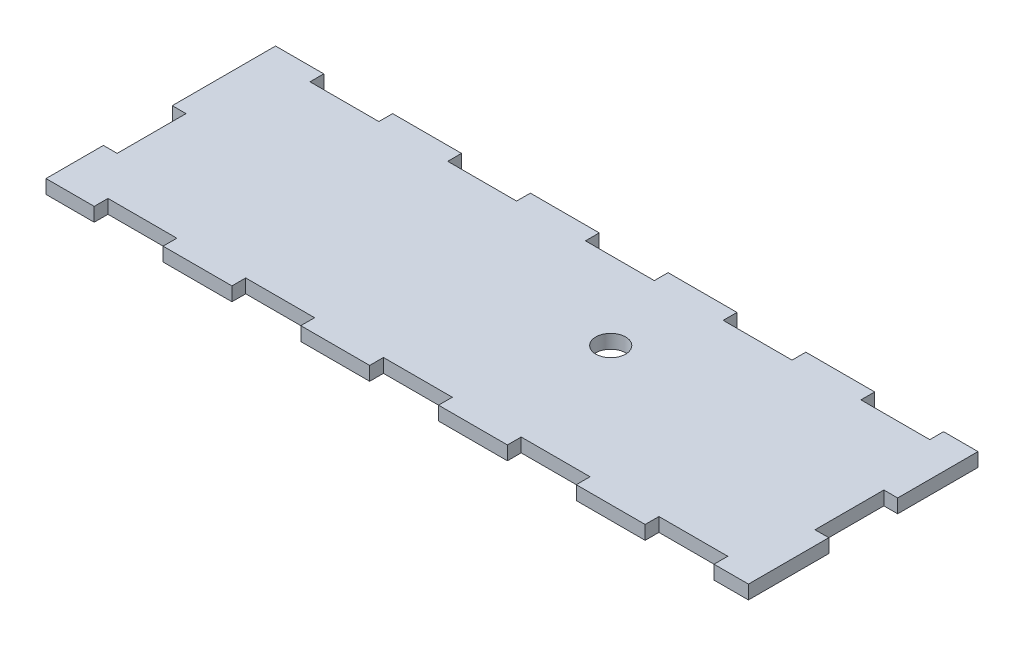
SolidWorks part; units mm, degrees
ref_plane "Alzado" through (0, 0, 0) normal (0, 0, 1) x (1, 0, 0)
ref_plane "Planta" through (0, 0, 0) normal (0, 1, 0) x (1, 0, 0)
ref_plane "Vista lateral" through (0, 0, 0) normal (1, 0, 0) x (0, 0, -1)
sketch "Croquis1" plane through (0, 0, 0) normal (0, 1, 0) x (1, 0, 0)
  line L0 (0, 0) -> (10.5, 0)
  line L1 (0, 40) -> (0, 50)
  line L2 (3, 50) -> (10.5, 50)
  line L3 (153, 50) -> (153, 32.5)
  line L4 (0, 0) -> (0, 12.5)
  line L6 (3, 20) -> (3, 27.5)
  line L7 (3, 27.5) -> (0, 27.5)
  line L8 (3, 20) -> (3, 12.5)
  line L9 (3, 12.5) -> (0, 12.5)
  line L11 (3, 50) -> (10.5, 50)
  line L12 (93, 50) -> (93, 30) construction
  line L13 (0, 27.5) -> (0, 40)
  line L14 (70.5, 50) -> (67.6088, 50)
  line L15 (85.5, 47) -> (70.5, 47)
  line L16 (70.5, 47) -> (70.5, 50)
  line L17 (70.5, 50) -> (55.5, 50)
  line L18 (55.5, 50) -> (55.5, 47)
  line L19 (55.5, 47) -> (40.5, 47)
  line L20 (40.5, 47) -> (40.5, 50)
  line L21 (40.5, 50) -> (25.5, 50)
  line L22 (25.5, 50) -> (25.5, 47)
  line L23 (25.5, 47) -> (10.5, 47)
  line L24 (10.5, 47) -> (10.5, 50)
  line L25 (145.5, 47) -> (145.5, 50)
  line L26 (130.5, 47) -> (145.5, 47)
  line L27 (130.5, 50) -> (130.5, 47)
  line L28 (115.5, 47) -> (115.5, 50)
  line L29 (100.5, 47) -> (115.5, 47)
  line L30 (100.5, 50) -> (100.5, 47)
  line L31 (85.5, 47) -> (85.5, 50)
  line L32 (0, 50) -> (3, 50)
  line L33 (150, 25) -> (150, 32.5)
  line L34 (150, 32.5) -> (153, 32.5)
  line L35 (150, 25) -> (150, 17.5)
  line L36 (150, 17.5) -> (153, 17.5)
  line L37 (25.5, 0) -> (40.5, 0)
  line L38 (85.5, 3) -> (85.5, 0)
  line L39 (100.5, 0) -> (100.5, 3)
  line L40 (100.5, 3) -> (115.5, 3)
  line L41 (115.5, 3) -> (115.5, 0)
  line L42 (130.5, 0) -> (130.5, 3)
  line L43 (130.5, 3) -> (145.5, 3)
  line L44 (145.5, 3) -> (145.5, 0)
  line L45 (10.5, 3) -> (10.5, 0)
  line L46 (25.5, 3) -> (10.5, 3)
  line L47 (25.5, 0) -> (25.5, 3)
  line L48 (40.5, 3) -> (40.5, 0)
  line L49 (55.5, 3) -> (40.5, 3)
  line L50 (55.5, 0) -> (55.5, 3)
  line L51 (70.5, 3) -> (70.5, 0)
  line L52 (85.5, 3) -> (70.5, 3)
  line L53 (55.5, 0) -> (70.5, 0)
  line L54 (85.5, 0) -> (100.5, 0)
  line L55 (115.5, 0) -> (130.5, 0)
  line L56 (145.5, 0) -> (153, 0)
  line L57 (153, 17.5) -> (153, 0)
  line L58 (145.5, 50) -> (153, 50)
  line L59 (115.5, 50) -> (130.5, 50)
  line L60 (85.5, 50) -> (100.5, 50)
  line L61 (85.5, 50) -> (93, 50)
  line L62 (55.5, 50) -> (70.5, 50)
  line L63 (55.5, 50) -> (70.5, 50)
  line L64 (25.5, 50) -> (40.5, 50)
  line L65 (25.5, 50) -> (40.5, 50)
  circle A0 centre (93, 30) radius 3.25
  dimension "D9" = 6.5
  dimension "D1" = 153
  dimension "D3" = 40
  dimension "D5" = 7.5
  dimension "D6" = 7.5
  dimension "D7" = 90
  dimension "D8" = 20
  dimension "D11" = 15
  dimension "D12" = 15
  dimension "D13" = 15
  dimension "D14" = 15
  dimension "D16" = 7.5
  dimension "D17" = 7.5
extrude "Saliente-Extruir1" add sketch "Croquis1" along normal blind 3 contours L60 L31 L15 L16 L14 L17 L18 L19 L20 L21 L22 L23 L24 L2 L13 L7 L6 L8 L9 L4 L0 L45 L46 L47 L37 L48 L49 L50 L53 L51 L52 L38 L54 L39 L40 L41 L55 L42 L43 L44 L56 L57 L36 L35 L33 L34 L3 L58 L25 region at (76.3272, 0, -25.0083)
